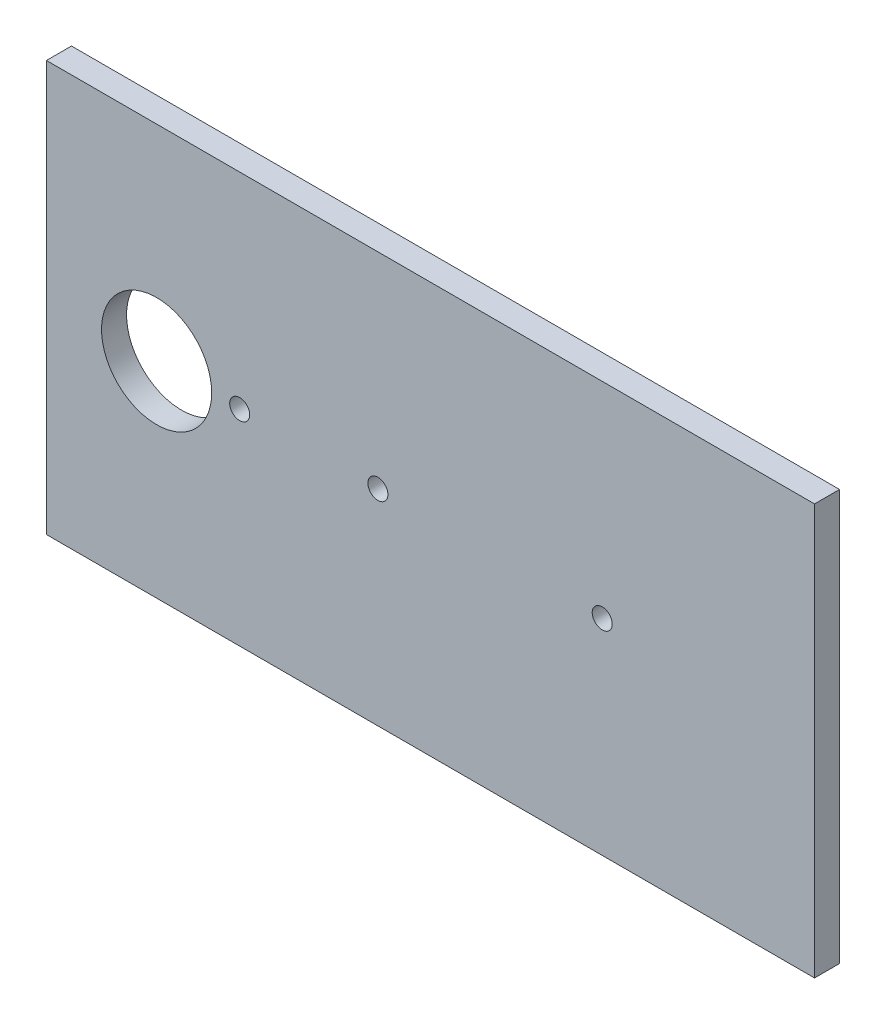
SolidWorks part; units mm, degrees
material "Сталь ШХ15 ГОСТ 801-78"
ref_plane "Plane1" through (0, 0, 0) normal (0, 0, 1) x (1, 0, 0)
ref_plane "Plane2" through (0, 0, 0) normal (0, 1, 0) x (1, 0, 0)
ref_plane "Plane3" through (0, 0, 0) normal (1, 0, 0) x (0, 0, -1)
sketch "Эскиз1" plane through (0, 0, 0) normal (0, 0, 1) x (1, 0, 0)
  line L0 (0, 41) -> (153.4, 41) construction
  line L1 (0, 0) -> (153.4, 0)
  line L2 (0, 0) -> (0, 82)
  line L3 (0, 82) -> (153.4, 82)
  line L4 (153.4, 0) -> (153.4, 82)
  circle A0 centre (22, 41) radius 11
  circle A1 centre (38.6, 41) radius 2
  circle A2 centre (66.2, 41) radius 2
  circle A3 centre (111, 41) radius 2
  point P9 (107, 21)
  point P10 (0, 21)
  point P11 (0, 0)
  point P12 (10.0784, 21)
  point P15 (23.7232, 21)
  point P18 (42.435, 21)
  point P21 (65.3836, 21)
  point P22 (0, 0)
  point P23 (0, 0)
  point P24 (89.3977, 21)
  point P25 (36.5556, 21)
  point P26 (20.846, 21)
  point P27 (0, 0)
  point P28 (0, 0)
  point P29 (83.7155, 21)
  dimension "D3" = 22
  dimension "D4" = 22
  dimension "D5" = 4
  dimension "D6" = 16.6
  dimension "D1" = 82
  dimension "D2" = 42.4
  dimension "D7" = 27.6
  dimension "D8" = 44.8
extrude "Бобышка-Вытянуть1" add sketch "Эскиз1" along normal blind 5 contours A0 L0 | L0 A0 | A1 L0 | L0 A1 | A2 L0 | L0 A2 | A3 L0 | L0 A3 | L2 L3 L4 L1 region at (111, 40.1512, 0) region at (111, 41.8488, 0) region at (66.2, 40.1512, 0) region at (66.2, 41.8488, 0) region at (38.6, 40.1512, 0) region at (38.6, 41.8488, 0) region at (22, 45.6685, 0) region at (22, 36.3315, 0)
